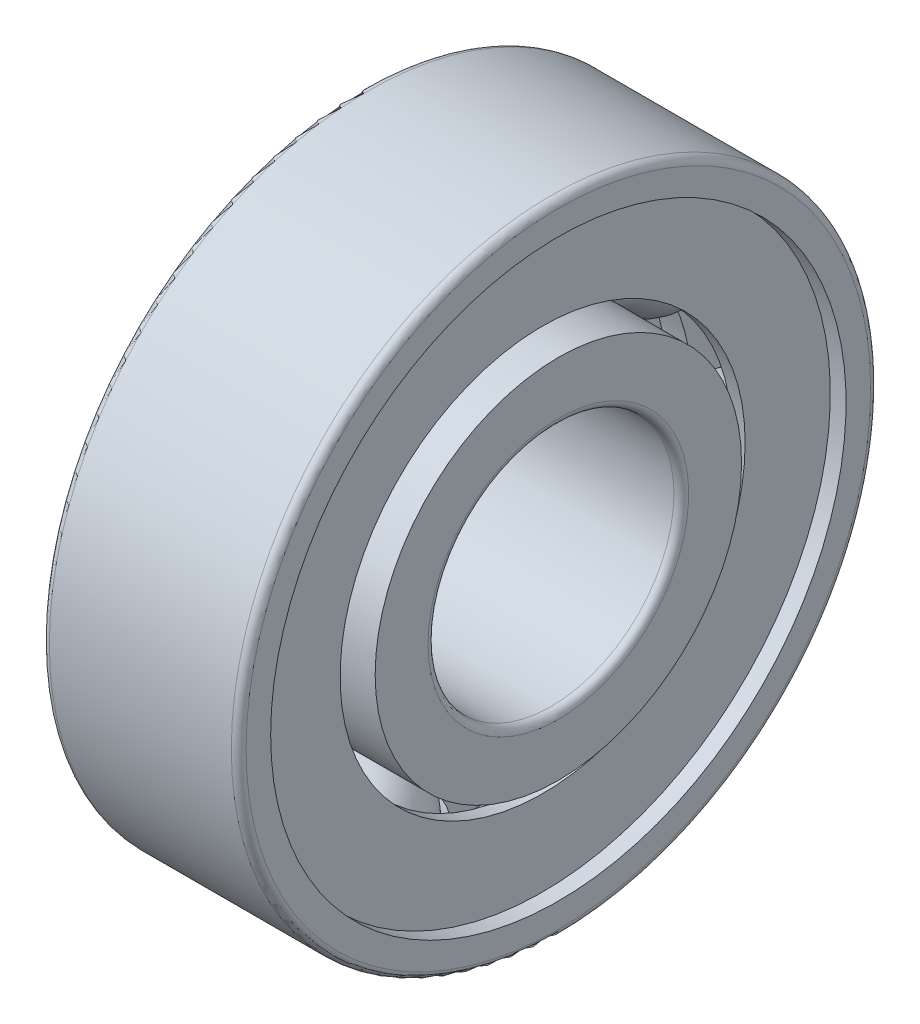
SolidWorks part; units mm, degrees
revolve "凸台-旋转2" add sketch "草图6" angle 360 about L4
sketch "草图6" plane through (0, 0, 0) normal (0, 0, 1) x (1, 0, 0)
  line L0 (0, 0) -> (5.5439, 0) construction
  line L1 (-12.4206, 0) -> (9.8128, 0) construction
  line L2 (0, 0) -> (0, 11.4011) construction
  line L3 (-5.5681, 9.575) -> (6.1049, 9.575) construction
  line L4 (-5.5681, 9.575) -> (6.1049, 9.575) construction
  line L5 (-2.381, 9.575) -> (2.381, 9.575)
  arc A0 (-2.381, 9.575) -> (2.381, 9.575) centre (0, 9.575) ccw
  dimension "Dw" = 4.762
revolve "基体-旋转" add sketch "草图2" angle 360 about L0
sketch "草图2" plane through (0, 0, 0) normal (0, 0, 1) x (1, 0, 0)
  line L0 (-12.4206, 0) -> (9.8128, 0) construction
  line L1 (0, 0) -> (0, 37.3563) construction
  line L2 (-5.5681, 9.575) -> (6.1049, 9.575) construction
  line L3 (-0.5238, 10.2298) -> (0.5238, 10.2298)
  line L4 (-0.5238, 10.2298) -> (-0.5238, 8.9202)
  line L5 (-0.5238, 8.9202) -> (0.5238, 8.9202)
  line L6 (0.5238, 10.2298) -> (0.5238, 8.9202)
  dimension "D1" = 1.0476
  dimension "D2" = 0.5238
  dimension "D3" = 1.3095
  dimension "D4" = 0.6548
  dimension "D5" = 9.575
revolve "凸台-旋转1" add sketch "草图3" angle 360 about L1
sketch "草图3" plane through (0, 0, 0) normal (0, 0, 1) x (1, 0, 0)
  line L0 (-5.5681, 9.575) -> (6.1049, 9.575) construction
  line L1 (-5.5681, 9.575) -> (6.1049, 9.575) construction
  line L2 (-12.4206, 0) -> (9.8128, 0) construction
  line L3 (-12.4206, 0) -> (9.8128, 0) construction
  line L4 (0, 0) -> (0, 37.3563) construction
  line L5 (0, 0) -> (0, 37.3563) construction
  line L6 (-2.6191, 9.575) -> (2.6191, 9.575)
  arc A0 (-2.6191, 9.575) -> (2.6191, 9.575) centre (0, 9.575) ccw
  dimension "Dwww" = 5.2382
  dimension "D2" = 2.6191
pattern_circular "阵列(圆周)1" count 7 over 360 about axis through (-12.4206, 0, 0) along (1, 0, 0) of "凸台-旋转1"
revolve "凸台-旋转3" add sketch "草图7" angle 360 about L0
sketch "草图7" plane through (0, 0, 0) normal (0, 0, 1) x (1, 0, 0)
  line L0 (0, 0) -> (6.6488, 0) construction
  line L1 (0, 0) -> (0, 16.8954) construction
  line L2 (-3.7, 13) -> (3.7, 13)
  line L3 (-4, 12.7) -> (-4, 11.7)
  line L4 (-4, 11.7) -> (-1.0517, 11.7)
  line L5 (4, 12.7) -> (4, 11.7)
  line L6 (1.0517, 11.7) -> (2.8248, 11.7)
  line L7 (3.36, 11.7) -> (4, 11.7)
  line L8 (2.8248, 11.3) -> (3.36, 11.3)
  line L9 (2.8248, 11.3) -> (2.8248, 11.7)
  line L11 (3.36, 11.3) -> (3.36, 11.7)
  arc A0 (-3.7, 13) -> (-4, 12.7) centre (-3.7, 12.7) ccw
  arc A1 (3.7, 13) -> (4, 12.7) centre (3.7, 12.7) cw
  arc A2 (2.2892, 10.2298) -> (-2.2892, 10.2298) centre (0, 9.575) ccw construction
  arc A3 (1.074, 11.7) -> (-0.0001, 11.956) centre (0, 9.575) ccw construction
  arc A4 (1.0517, 11.7) -> (-1.0517, 11.7) centre (0, 9.575) ccw
  point P10 (-4, 13)
  point P13 (4, 13)
  dimension "D3" = 4
  dimension "D4" = 0.5352
  dimension "D5" = 22.6
  dimension "D6" = 0.64
  dimension "B" = 8
ref_plane "基准面1" through (0, 0, 0) normal (0, 0, 1) x (1, 0, 0)
ref_plane "基准面2" through (0, 0, 0) normal (0, 1, 0) x (1, 0, 0)
ref_plane "基准面3" through (0, 0, 0) normal (1, 0, 0) x (0, 0, -1)
sketch "尺寸草图" plane through (0, 0, 0) normal (0, 0, 1) x (1, 0, 0)
  point P0 (0, -75.4307)
  point P1 (4.762, -75.4307)
  point P2 (0, 50.7088)
  point P3 (10, 50.7088)
  point P4 (26, 50.7088)
  point P5 (8, 50.7088)
  point P6 (0, -10.9899)
  point P7 (14.9, -10.9899)
  point P8 (22.6, -10.9899)
  point P9 (0.3, -10.9899)
  point P10 (7, -75.4307)
  dimension "B" = 8
sketch "草图4" plane through (0, 0, 0) normal (0, 0, 1) x (1, 0, 0)
  line L0 (0, 0) -> (8.1272, 0) construction
  line L1 (-12.4206, 0) -> (9.8128, 0) construction
  line L3 (-0.5238, 10.2298) -> (0.5238, 10.2298) construction
  line L4 (-2.6191, 12.8489) -> (2.6191, 12.8489)
  line L5 (-2.6191, 12.8489) -> (-2.6191, 10.2298)
  line L6 (-2.6191, 10.2298) -> (2.6191, 10.2298)
  line L7 (2.6191, 12.8489) -> (2.6191, 10.2298)
revolve "切除-旋转1" cut sketch "草图4" angle 360 about L0
sketch "草图5" plane through (0, 0, 0) normal (0, 0, 1) x (1, 0, 0)
  line L0 (0, 0) -> (8.2665, 0) construction
  line L1 (-12.4206, 0) -> (9.8128, 0) construction
  line L2 (-0.5238, 8.9202) -> (0.5238, 8.9202) construction
  line L3 (-2.6191, 8.9202) -> (2.6191, 8.9202)
  line L4 (-2.6191, 8.9202) -> (-2.6191, 6.3011)
  line L5 (-2.6191, 6.3011) -> (2.6191, 6.3011)
  line L6 (2.6191, 8.9202) -> (2.6191, 6.3011)
revolve "切除-旋转2" cut sketch "草图5" angle 360 about L0
pattern_circular "阵列(圆周)2" count 7 over 360 about axis through (-12.4206, 0, 0) along (1, 0, 0) of "凸台-旋转2"
sketch "草图8" plane through (0, 0, 0) normal (0, 0, 1) x (1, 0, 0)
  line L0 (-12.4206, 0) -> (9.8128, 0) construction
  line L1 (-12.4206, 0) -> (9.8128, 0) construction
  line L2 (4, 12.7) -> (4, 11.7) construction
  line L3 (-4, 7.45) -> (-1.0517, 7.45)
  line L4 (-4, 7.45) -> (-4, 5.3)
  line L5 (-3.7, 5) -> (3.7, 5)
  line L6 (4, 7.45) -> (4, 5.3)
  line L7 (-4, 12.7) -> (-4, 11.7) construction
  line L8 (1.0517, 7.45) -> (4, 7.45)
  arc A0 (-4, 5.3) -> (-3.7, 5) centre (-3.7, 5.3) ccw
  arc A1 (3.7, 5) -> (4, 5.3) centre (3.7, 5.3) ccw
  arc A2 (-2.2892, 8.9202) -> (2.2892, 8.9202) centre (0, 9.575) ccw construction
  arc A3 (-2.2892, 8.9202) -> (2.2892, 8.9202) centre (0, 9.575) ccw construction
  arc A4 (-1.0517, 7.45) -> (1.0517, 7.45) centre (0, 9.575) ccw
  dimension "D1" = 0.3
  dimension "DD" = 10
  dimension "D2" = 0.01
revolve "凸台-旋转4" add sketch "草图8" angle 360 about L1
sketch "草图10" plane through (0, 0, 0) normal (0, 0, 1) x (1, 0, 0)
  line L0 (2.8248, 11.7) -> (2.8248, -11.7) construction
  line L1 (3.36, 11.3) -> (2.8248, 11.3)
  line L2 (3.36, 11.3) -> (3.36, 8.2357)
  line L3 (3.36, 8.2357) -> (2.8248, 8.2357)
  line L4 (2.8248, 11.3) -> (2.8248, 8.2357)
  line L5 (1.0517, 7.45) -> (4, 7.45) construction
  line L6 (0, 0) -> (-5.3515, 0) construction
  line L7 (-12.4206, 0) -> (9.8128, 0) construction
  dimension "D1" = 0.7857
revolve "凸台-旋转5" add sketch "草图10" angle 360 about L6
sketch "草图11" plane through (0, 0, 0) normal (1, 0, 0) x (0, 0, -1)
  circle A0 centre (0, 0) radius 13
  circle A1 centre (0, 0) radius 13 construction
extrude "切除-拉伸1" cut sketch "草图11" against normal blind 10
mirror "镜向所有1" about plane through (0, 0, 0) normal (1, 0, 0) of bodies 109
equation "\"D5@草图7\" = \"防尘圈径D3@尺寸草图\""
equation "\"Z@阵列(圆周)1\"=\"球数Z@尺寸草图\" "
equation "\"Dw@草图6\"=\"球径DW@尺寸草图\""
equation "\"DD@草图8\"=\"d@尺寸草图\""
equation "\"D@草图7\"=\"DD@尺寸草图\""
equation "\"B@草图7\"=\"B@尺寸草图\" "
equation "\"DD2@草图8\"=\"内圈外径DD2@尺寸草图\""
equation "\"R@草图7\"=\"r@尺寸草图\""
equation "\"D3@草图2\" = 0.25*\"Dwww@草图3\""
equation "\"D4@草图2\" = \"D3@草图2\"/2"
equation "\"Dwww@草图3\" = 1.1*\"Dw@草图6\""
equation "\"D2@草图3\" = 0.5*\"Dwww@草图3\""
equation "\"D1@草图2\" = 0.2*\"Dwww@草图3\""
equation "\"D2@草图2\" = 0.5*\"D1@草图2\""
equation "\"切除位置@草图4\" = \"Dwww@草图3\"/2"
equation "\"D1@阵列(圆周)2\" = \"Z@阵列(圆周)1\""
equation "\"D3@草图7\" = \"B@草图7\" / 2"
equation "\"D1@草图8\" = \"R@草图7\""
equation "\"D2@草图7\" = 0.9*\"D@草图7\""
equation "\"D5@草图2\" = 0.25* ( \"D2@草图7\" + \"DD2@草图8\" )  "
equation "\"D6@草图7\" = 0.08 * \"B@草图7\""
equation "\"D1@草图10\" = 0.15*\"Dwww@草图3\""
